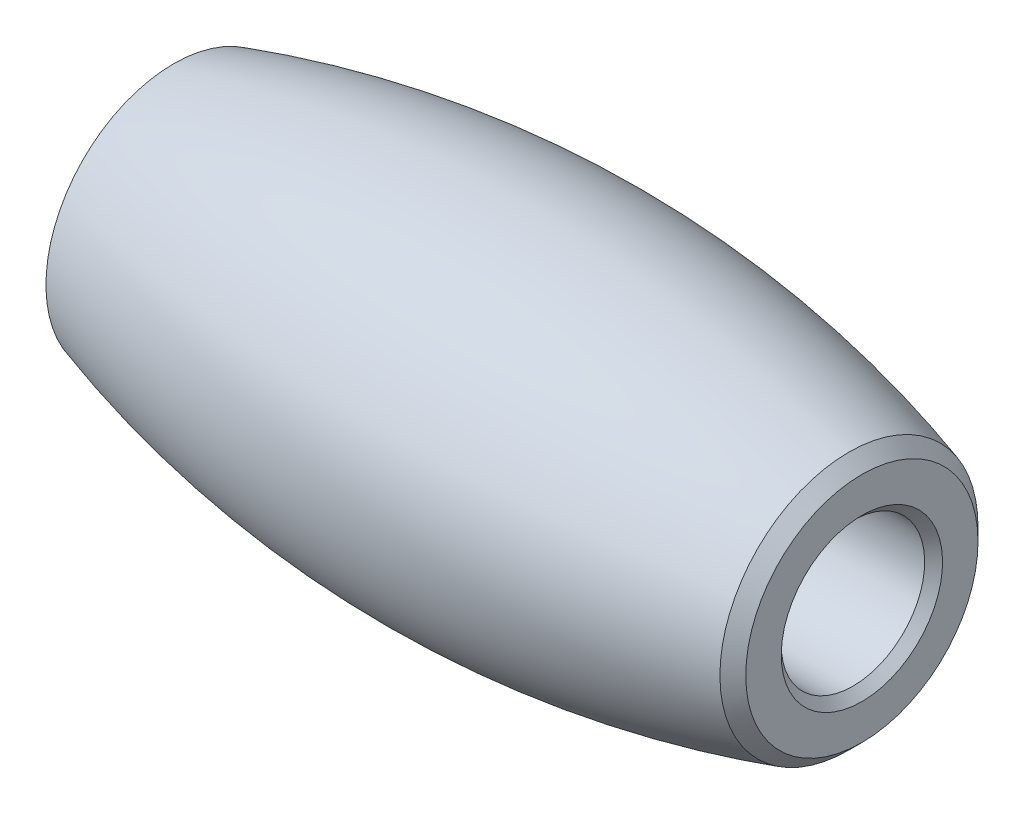
SolidWorks part; units mm, degrees
ref_plane "Front Plane" through (0, 0, 0) normal (0, 0, 1) x (1, 0, 0)
ref_plane "Top Plane" through (0, 0, 0) normal (0, 1, 0) x (1, 0, 0)
ref_plane "Right Plane" through (0, 0, 0) normal (1, 0, 0) x (0, 0, -1)
sketch "Sketch1" plane through (0, 0, 0) normal (0, 0, 1) x (1, 0, 0)
  line L0 (19.5, 7) -> (19.5, 4.015)
  line L1 (9.5, 3) -> (-9.5, 3)
  line L2 (-19.5, 4.015) -> (-19.5, 7)
  line L3 (-19.5, 0) -> (19.5, 0) construction
  line L4 (-9.5, 3) -> (-9.5, 4.015)
  line L5 (-9.5, 4.015) -> (-19.5, 4.015)
  line L6 (19.5, 4.015) -> (9.5, 4.015)
  line L7 (9.5, 4.015) -> (9.5, 3)
  arc A0 (-19.5, 7) -> (19.5, 7) centre (0, -54.875) cw
  point P3 (0, 10)
  point P10 (0, 0)
  dimension "D1" = 3
  dimension "D2" = 39
  dimension "D3" = 10
  dimension "D4" = 7
  dimension "D5" = 4.015
  dimension "D6" = 10
  dimension "D8" = 10
revolve "Revolve1" add sketch "Sketch1" angle 360 about L3
chamfer "Chamfer1" distance 0.5 angle 45 4 edges at (19.5, -7, 0) (-19.5, -7, 0) (-19.5, -4.015, 0) (19.5, -4.015, 0)
